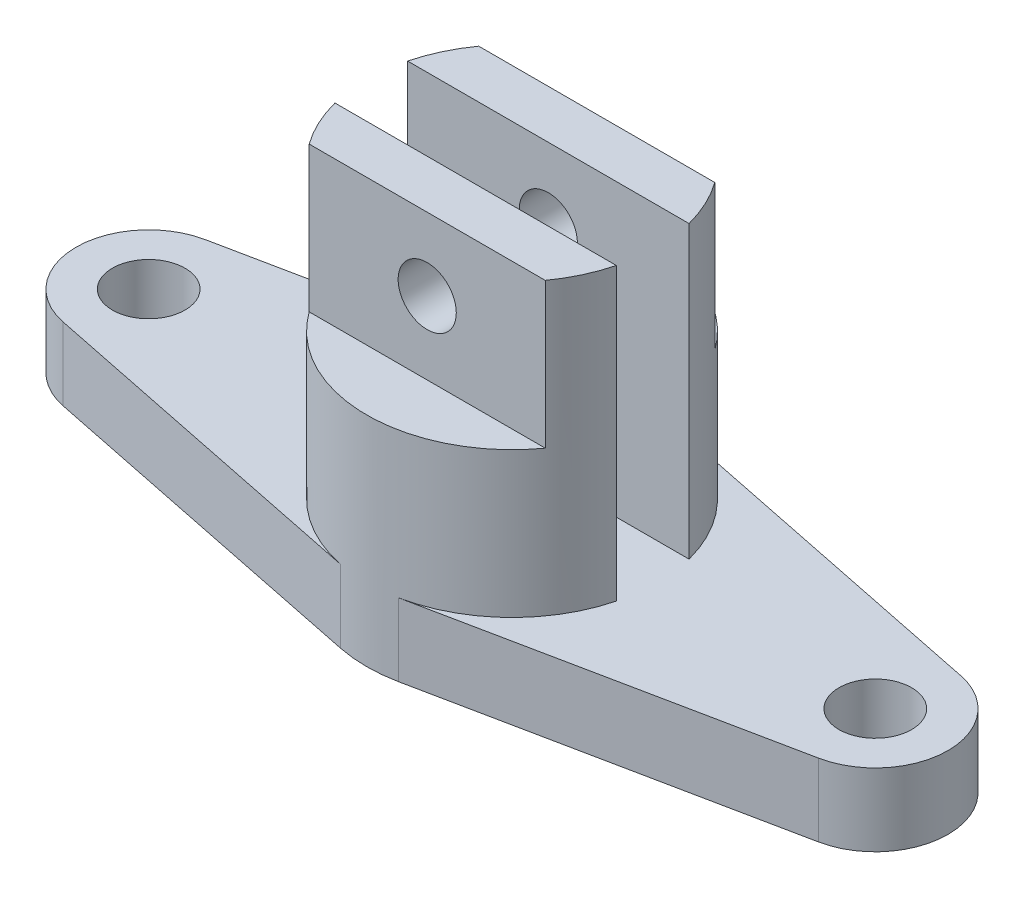
SolidWorks part; units mm, degrees
ref_plane "Front Plane" through (0, 0, 0) normal (0, 0, 1) x (1, 0, 0)
ref_plane "Top Plane" through (0, 0, 0) normal (0, 1, 0) x (1, 0, 0)
ref_plane "Right Plane" through (0, 0, 0) normal (1, 0, 0) x (0, 0, -1)
sketch "Sketch1" plane through (0, 0, 0) normal (0, 1, 0) x (1, 0, 0)
  line L0 (0, 7.5) -> (0, 30) construction
  line L1 (-24.367, 17.5) -> (24.367, 17.5)
  line L2 (29.0474, -7.5) -> (-29.0474, -7.5)
  line L4 (29.0474, 7.5) -> (-29.0474, 7.5)
  line L6 (0, 0) -> (-75, 0) construction
  line L7 (-24.367, -17.5) -> (24.367, -17.5)
  line L8 (-78, 14.6969) -> (-6, 29.3939)
  line L9 (-78, -14.6969) -> (-6, -29.3939)
  line L10 (78, -14.6969) -> (6, -29.3939)
  line L11 (78, 14.6969) -> (6, 29.3939)
  arc A0 (-29.0474, -7.5) -> (29.0474, -7.5) centre (0, 0) ccw
  circle A1 centre (-75, 0) radius 7.5
  circle A2 centre (75, 0) radius 7.5
  arc A3 (29.0474, 7.5) -> (-29.0474, 7.5) centre (0, 0) ccw
  arc A4 (-78, 14.6969) -> (-78, -14.6969) centre (-75, 0) ccw
  arc A5 (78, -14.6969) -> (78, 14.6969) centre (75, 0) ccw
  point P17 (-75.7206, 0)
  point P21 (-78.8798, 19.7348)
  point P22 (0, 0)
  point P23 (0, 0)
  dimension "D1" = 60
  dimension "D2" = 15
  dimension "D3" = 15
  dimension "D4" = 150
  dimension "D8" = 30
  dimension "D5" = 15
  dimension "D6" = 35
  dimension "D7" = 7.5
extrude "Boss-Extrude1" add sketch "Sketch1" along normal blind 75 contours L4 A3 L1 | L7 A0 L2 region at (0, 0, -12.3572) region at (0, 0, 12.3572)
extrude "Boss-Extrude2" add sketch "Sketch1<4>" along normal blind 45 contours A0 L7 | L1 A3 region at (0, 0, -22.6016) region at (0, 0, 22.6016)
sketch "Sketch1<4>" plane through (0, 0, 0) normal (0, 1, 0) x (1, 0, 0) same geometry as "Sketch1"
extrude "Boss-Extrude3" add sketch "Sketch1<5>" along normal blind 15 contours L10 A5 L11 A3 L4 L8 A4 L9 A0 L2 A1 A2 region at (0, 0, 0)
sketch "Sketch1<5>" plane through (0, 0, 0) normal (0, 1, 0) x (1, 0, 0) same geometry as "Sketch1"
sketch "Sketch2" plane through (0, 0, 17.5) normal (0, 0, 1) x (1, 0, 0)
  line L0 (78, 0) -> (6, 0) construction
  line L1 (-90, 15) -> (-90, 0) construction
  circle A0 centre (0, 60) radius 6
  dimension "D1" = 12
  dimension "D2" = 60
  dimension "D3" = 90
extrude "Cut-Extrude1" cut sketch "Sketch2" against normal through all
